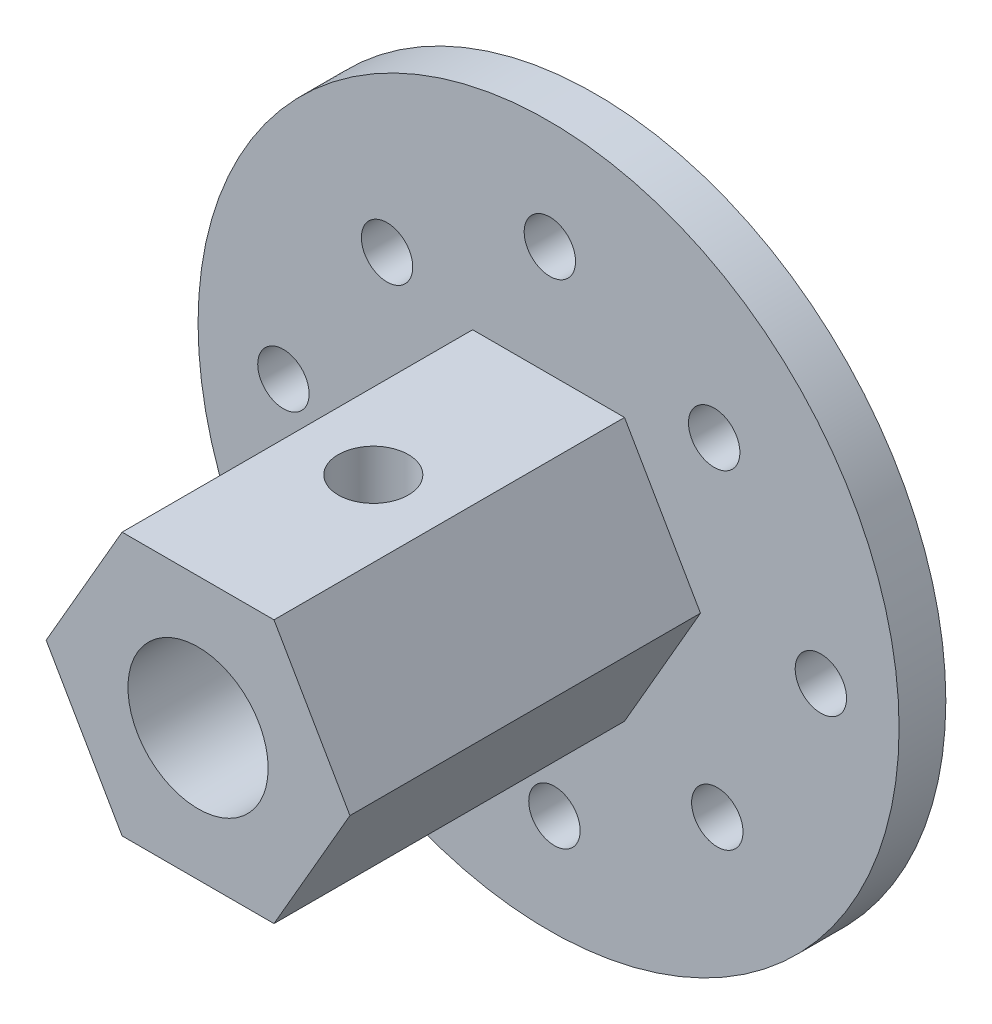
SolidWorks part; units mm, degrees
ref_plane "前视基准面" through (0, 0, 0) normal (0, 0, 1) x (1, 0, 0)
ref_plane "上视基准面" through (0, 0, 0) normal (0, 1, 0) x (1, 0, 0)
ref_plane "右视基准面" through (0, 0, 0) normal (1, 0, 0) x (0, 0, -1)
other "Configuration Table"
sketch "草图1" plane through (0, 0, 0) normal (0, 0, 1) x (1, 0, 0)
  line L1 (6.5, 0) -> (3.25, 5.6292)
  line L2 (3.25, 5.6292) -> (-3.25, 5.6292)
  line L3 (-3.25, 5.6292) -> (-6.5, 0)
  line L4 (-6.5, 0) -> (-3.25, -5.6292)
  line L5 (-3.25, -5.6292) -> (3.25, -5.6292)
  line L6 (3.25, -5.6292) -> (6.5, 0)
  circle A1 centre (0, 0) radius 6.5 construction
  circle A2 centre (0, 0) radius 3
extrude "凸台-拉伸1" add sketch "草图1" along normal blind 15 contours L5 L6 L1 L2 L3 L4 A2 region at (4.7261, -2.7286, 0)
sketch "草图2" plane through (0, 0, 0) normal (0, 0, -1) x (-1, 0, 0)
  circle A0 centre (0, 0) radius 15
  circle A1 centre (0, 0) radius 3.1
  circle A2 centre (-0.0547, 10.3603) radius 1.1
  circle A3 centre (6.9122, 6.6679) radius 1.1
  circle A4 centre (11.3468, -0.2466) radius 1.1
  circle A5 centre (6.7799, -7.3319) radius 1.1
  circle A6 centre (-0.2505, -10.6388) radius 1.1
  circle A7 centre (-7.2201, -7.201) radius 1.1
  circle A8 centre (-11.6522, -0.0321) radius 1.1
  circle A9 centre (-7.087, 6.7958) radius 1.1
  dimension "D1" = 2.2
  dimension "D2" = 2.2
  dimension "D3" = 2.2
  dimension "D4" = 2.2
  dimension "D5" = 2.2
  dimension "D6" = 2.2
  dimension "D7" = 2.2
  dimension "D8" = 2.2
  dimension "D9" = 6.2
extrude "凸台-拉伸2" add sketch "草图2" along normal blind 2
sketch "草图3" plane through (0, 5.6292, 0) normal (0, 1, 0) x (1, 0, 0)
  line L0 (3.25, -7.5) -> (-3.25, -7.5) construction
  line L1 (3.25, -15) -> (3.25, 0) construction
  line L2 (-3.25, -15) -> (-3.25, 0) construction
  circle A0 centre (0, -7.5) radius 1.5
extrude "切除-拉伸1" cut sketch "草图3" against normal through all
